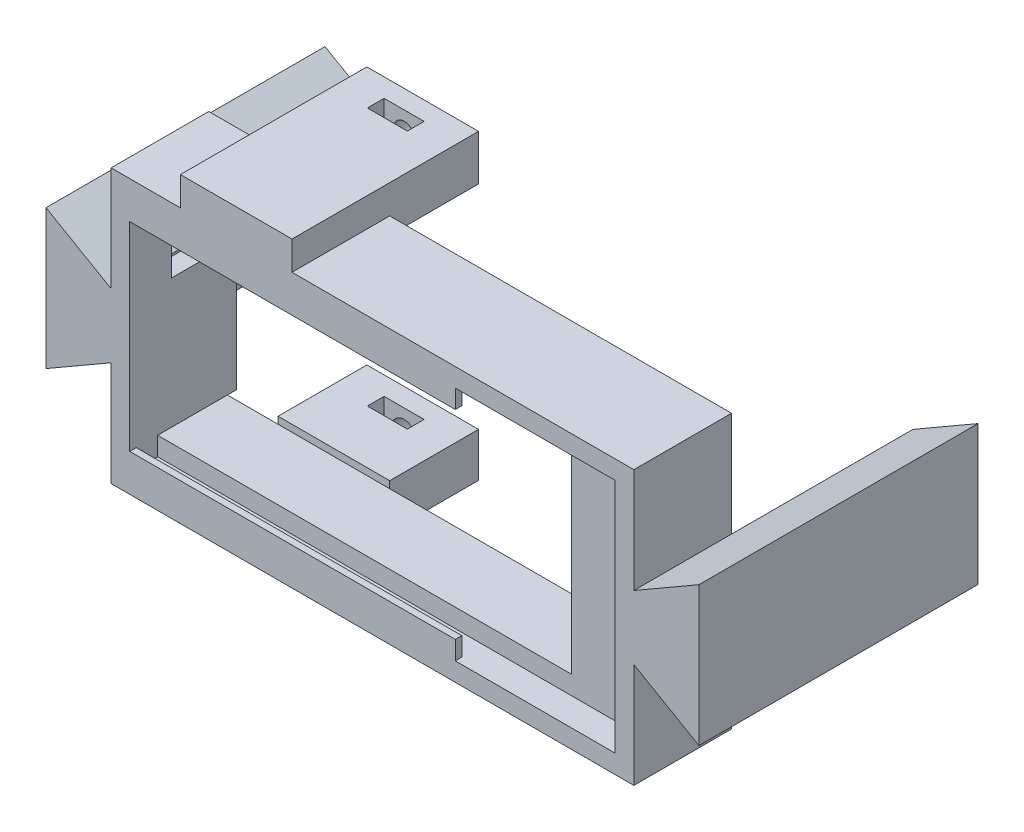
SolidWorks part; units mm, degrees
ref_plane "Front Plane" through (0, 0, 0) normal (0, 0, 1) x (1, 0, 0)
ref_plane "Top Plane" through (0, 0, 0) normal (0, 1, 0) x (1, 0, 0)
ref_plane "Right Plane" through (0, 0, 0) normal (1, 0, 0) x (0, 0, -1)
sketch "Sketch1" plane through (0, 0, 0) normal (0, 0, 1) x (1, 0, 0)
  line L0 (24.1, 10.7) -> (-24.1, 10.7)
  line L1 (26.1, -12.7) -> (-26.1, -12.7)
  line L2 (26.1, -12.7) -> (26.1, 12.7)
  line L3 (26.1, 12.7) -> (-26.1, 12.7)
  line L4 (-26.1, -12.7) -> (-26.1, 12.7)
  line L5 (26.1, -12.7) -> (-26.1, 12.7) construction
  line L6 (26.1, 12.7) -> (-26.1, -12.7) construction
  line L7 (-24.1, -10.7) -> (-24.1, 10.7)
  line L8 (24.1, -10.7) -> (-24.1, -10.7)
  line L9 (24.1, -10.7) -> (24.1, 10.7)
  line L10 (18.4, 10.7) -> (18.4, -10.7)
  point P0 (0, 0)
  dimension "D1" = 25.4
  dimension "D2" = 52.2
  dimension "D4" = 5.7
  dimension "D3" = 2
extrude "Boss-Extrude1" add sketch "Sketch1" along normal blind 7.5 contours L0 L10 L8 L9 | L4 L1 L2 L3 L9 L8 L7 L0 region at (21.25, 0, 0) region at (0, -12.1195, 0)
sketch "Sketch2" plane through (0, 0, 7.5) normal (0, 0, 1) x (1, 0, 0)
  line L12 (-26.1, -12.7) -> (-26.1, 12.7) construction
  line L13 (26.1, 12.7) -> (-26.1, 12.7) construction
  line L14 (26.1, -12.7) -> (-26.1, -12.7) construction
  line L15 (26.1, -12.7) -> (26.1, 12.7) construction
  line L16 (26.1, -12.7) -> (-26.1, -12.7)
  line L17 (-26.1, -12.7) -> (-26.1, 12.7)
  line L18 (26.1, 12.7) -> (-26.1, 12.7)
  line L19 (26.1, -12.7) -> (26.1, 12.7)
  line L20 (28.1, 14.7) -> (-28.1, 14.7)
  line L21 (-28.1, -14.7) -> (-28.1, 14.7)
  line L22 (28.1, -14.7) -> (-28.1, -14.7)
  line L23 (28.1, -14.7) -> (28.1, 14.7)
  line M29 (-26.1, 12.7) -> (-26.1, -12.7)
  line M30 (-26.1, -12.7) -> (26.1, -12.7)
  line M31 (26.1, -12.7) -> (26.1, 12.7)
  line M32 (26.1, 12.7) -> (-26.1, 12.7)
  dimension "D1" = 2
extrude "Boss-Extrude2" add sketch "Sketch2" along normal blind 3 and the other way up to surface (7.5 mm away) contours L22 L23 L20 L21 M29 M32 M31 M30 region at (27.4657, 0, 7.5) other way up to face at (-2.85, 0, 0)
sketch "Sketch3" plane through (0, 0, 0) normal (0, 0, 1) x (1, 0, 0)
  line L3 (-20.65, -11.4) -> (-8.65, -11.4)
  line L5 (-8.65, 11.4) -> (-20.65, 11.4)
  line L6 (-20.65, 11.4) -> (-20.65, -11.4)
  line L7 (-8.65, 11.4) -> (-8.65, -11.4)
  line L9 (-24.1, -10.7) -> (-24.1, 10.7) construction
  circle A0 centre (-14.65, 6.7) radius 2.5
  point P2 (-8.65, 0)
  point P10 (-14.65, 11.4)
  dimension "D1" = 5
  dimension "D3" = 4.7
  dimension "D2" = 12
  dimension "D4" = 22.8
  dimension "D5" = 9.45
sketch "Sketch4" plane through (0, 0, 0) normal (0, 0, -1) x (-1, 0, 0)
  line L2 (8.65, -11.4) -> (8.65, -16.25)
  line L3 (8.65, -16.25) -> (20.65, -16.25)
  line L18 (8.65, 16.25) -> (20.65, 16.25)
  line L20 (20.65, -16.25) -> (8.65, -16.25)
  line L22 (20.65, -11.4) -> (8.65, -11.4) construction
  line L23 (20.65, 11.4) -> (20.65, -11.4) construction
  line L24 (20.65, -16.25) -> (20.65, -11.4)
  line L25 (20.65, 11.4) -> (20.65, 16.25)
  line L26 (20.65, 16.25) -> (8.65, 16.25)
  line L27 (8.65, 16.25) -> (8.65, 11.4)
  line L28 (8.65, 11.4) -> (20.65, 11.4) construction
  line L29 (8.65, 11.4) -> (8.65, -11.4) construction
  line L30 (20.65, -11.4) -> (8.65, -11.4)
  line L31 (20.65, 11.4) -> (20.65, -11.4)
  line L32 (8.65, 11.4) -> (20.65, 11.4)
  line L33 (8.65, 11.4) -> (8.65, -11.4)
  point P3 (3.7, 16.25)
  point P5 (25.4, 16.25)
  point P6 (25.4, -16.25)
  point P7 (3.7, -16.25)
  dimension "D1" = 4.85
  dimension "D2" = 4.85
extrude "Boss-Extrude4" [suppressed] add sketch "Sketch4" along normal blind 3 and the other way up to surface separate body
sketch "Sketch6" plane through (0, 0, 10.5) normal (0, 0, 1) x (1, 0, 0)
  line L1 (-28.1, 3.45) -> (-35.1, 7.4915)
  line L5 (-28.1, -14.7) -> (-28.1, 14.7) construction
  line L7 (-35.1, 7.4915) -> (-35.1, -7.4915)
  line L8 (0, 10.5) -> (0, 0) construction
  line L16 (-35.1, -7.4915) -> (-28.1, -3.45)
  line L17 (-28.1, 3.45) -> (-28.1, -3.45)
  point P6 (-35.1, 0)
  dimension "D1" = 7
  dimension "D2" = 6.9
  dimension "D3" = 60
  dimension "D4" = 60
extrude "Boss-Extrude5" add sketch "Sketch6" against normal blind 30
mirror "Mirror1" about plane through (0, 0, 0) normal (1, 0, 0) of "Boss-Extrude5"
ref_plane "Plane1" through (-8.65, 0, 0) normal (1, 0, 0) x (0, 0, -1)
ref_plane "Plane2" through (-20.65, 0, 0) normal (1, 0, 0) x (0, 0, -1)
sketch "Sketch10" plane through (-8.65, 0, 0) normal (1, 0, 0) x (0, 0, -1)
  line L1 (9.55, 17.8) -> (-10.5, 17.8)
  line L3 (0, 14.7) -> (-10.5, 14.7)
  line L6 (-10.5, 14.7) -> (-10.5, 17.8)
  line L7 (19.5, 7.4915) -> (-10.5, 7.4915) construction
  line L8 (0, 12.9) -> (0, 14.7)
  line L9 (0, 12.9) -> (9.55, 12.9)
  line L10 (9.55, 12.9) -> (9.55, 17.8)
  dimension "D3" = 3.1
  dimension "D4" = 5.4085
extrude "Boss-Extrude12" add sketch "Sketch10" against normal up to surface (12 mm away) contours L9 L10 L1 L8 region at (-8.65, 15.7192, -0.6624) up to plane "Plane2"
sketch "Sketch11" plane through (0, 0, -9.55) normal (0, 0, -1) x (-1, 0, 0)
  line L0 (14.1, 17.8) -> (14.1, 16.6)
  line L1 (20.65, 17.8) -> (8.65, 17.8) construction
  line L3 (15.2, 16.6) -> (15.2, 17.8)
  line L4 (20.65, 17.8) -> (8.65, 17.8)
  arc A0 (15.2, 16.6) -> (14.1, 16.6) centre (14.65, 15.6474) cw
  arc A1 (14.1, 16.6) -> (15.2, 16.6) centre (14.65, 15.6474) cw
  point P8 (14.65, 17.8)
  dimension "D3" = 1.1
  dimension "D1" = 1.1
  dimension "D2" = 1.2
extrude "Cut-Extrude2" cut sketch "Sketch11" against normal blind 16 contours A1 A0 region at (-14.65, 15.6474, -9.55)
sketch "Sketch12" plane through (0, 17.8, 0) normal (0, 1, 0) x (1, 0, 0)
  line L0 (-13.55, 9.55) -> (-15.75, 9.55) construction
  line L1 (-13.55, 9.55) -> (-15.75, 9.55)
  line L3 (-12.5, 5.75) -> (-16.8, 5.75)
  line L4 (-16.8, 5.75) -> (-16.8, 7.55)
  line L5 (-16.8, 7.55) -> (-12.5, 7.55)
  line L6 (-12.5, 7.55) -> (-12.5, 5.75)
  point P7 (-14.65, 7.55)
  point P8 (-14.65, 9.55)
  dimension "D1" = 2
  dimension "D2" = 1.8
  dimension "D3" = 4.3
extrude "Cut-Extrude3" cut sketch "Sketch12" against normal up to next contours L6 L5 L4 L3 region at (-14.65, 17.8, -6.65)
sketch "Sketch13" plane through (-8.65, 0, 0) normal (1, 0, 0) x (0, 0, -1)
  line L4 (0, -14.7) -> (0, -9.95)
  line L8 (0, -9.95) -> (9.55, -9.95)
  line L9 (9.55, -9.95) -> (9.55, -14.7)
  line L10 (9.55, -14.7) -> (0, -14.7)
  line L11 (0, -14.7) -> (-10.5, -14.7) construction
  line L12 (0, 11.4) -> (0, -11.4) construction
  dimension "D1" = 4.75
  dimension "D3" = 9.55
extrude "Boss-Extrude14" add sketch "Sketch13" against normal up to surface (12 mm away) separate body contours L10 L9 L8 L4 region at (-8.65, -12.325, -4.775) up to plane "Plane2"
sketch "Sketch8" plane through (0, 0, 0) normal (0, 0, -1) x (-1, 0, 0)
  line L1 (-18.4, 10.7) -> (-26.1, 10.7)
  line L2 (-18.4, 10.7) -> (-18.4, -10.7)
  line L3 (-18.4, -10.7) -> (-26.1, -10.7)
  line L4 (-26.1, 10.7) -> (-26.1, -10.7)
  line L5 (-18.4, -10.7) -> (24.1, -10.7) construction
  line L6 (-28.1, 14.7) -> (-28.1, 3.45) construction
  dimension "D1" = 2
extrude "Boss-Extrude6" [suppressed] add sketch "Sketch8" along normal blind 3.5
sketch "Sketch9" [suppressed] plane through (0, 0, -3.5) normal (0, 0, -1) x (-1, 0, 0)
  line L0 (-18.4, 10.7) -> (-26.1, 10.7) construction
  line L1 (-18.4, 10.7) -> (-26.1, 10.7)
  circle A0 centre (-22.25, 0) radius 2.65
  point P7 (-22.25, 10.7)
  dimension "D1" = 5.3
extrude "Cut-Extrude1" [suppressed] cut sketch "Sketch9" against normal through all contours A0
sketch "Sketch14" plane through (0, 0, -9.55) normal (0, 0, -1) x (-1, 0, 0)
  line L0 (14.1, -14.7) -> (14.1, -13.5)
  line L1 (20.65, -14.7) -> (8.65, -14.7) construction
  line L2 (15.2, -14.7) -> (15.2, -13.5)
  line L3 (15.2, -14.7) -> (14.1, -14.7)
  line L4 (20.65, -14.7) -> (8.65, -14.7)
  circle A1 centre (14.65, -12.3221) radius 1.3
  point P8 (14.65, -14.7)
  point P9 (14.65, -14.7)
  dimension "D3" = 2.6
  dimension "D1" = 1.1
  dimension "D2" = 1.2
extrude "Cut-Extrude4" cut sketch "Sketch14" against normal blind 16 contours A1 region at (-14.65, -12.3221, -9.55)
sketch "Sketch15" plane through (0, -14.7, 0) normal (0, -1, 0) x (1, 0, 0)
  line L0 (-16.8, -7.55) -> (-12.5, -7.55) construction
  line L1 (-12.5, -7.55) -> (-12.5, -5.75) construction
  line L2 (-12.5, -5.75) -> (-16.8, -5.75) construction
  line L3 (-16.8, -5.75) -> (-16.8, -7.55) construction
  line L4 (-16.8, -7.55) -> (-12.5, -7.55)
  line L5 (-12.5, -7.55) -> (-12.5, -5.75)
  line L6 (-12.5, -5.75) -> (-16.8, -5.75)
  line L7 (-16.8, -5.75) -> (-16.8, -7.55)
extrude "Cut-Extrude5" cut sketch "Sketch15" against normal blind 10
sketch "Sketch16" plane through (0, 0, 0) normal (0, 0, -1) x (-1, 0, 0)
  line L0 (24.1, 10.7) -> (28.1, 10.7)
  line L2 (24.1, -10.7) -> (24.1, 10.7)
  line L3 (24.1, -10.7) -> (28.1, -10.7)
  line L4 (28.1, -10.7) -> (28.1, 10.7)
  line L7 (28.1, 14.7) -> (28.1, 3.45) construction
extrude "Cut-Extrude6" cut sketch "Sketch16" against normal blind 4
sketch "Sketch17" plane through (0, 0, 10.5) normal (0, 0, 1) x (1, 0, 0)
  line L0 (8.9, 12.7) -> (-26.1, 12.7)
  line L1 (26.1, 12.7) -> (-26.1, 12.7) construction
  line L2 (-26.1, 12.7) -> (-26.1, -12.7)
  line L3 (-26.1, -12.7) -> (8.9, -12.7)
  line L4 (-26.1, -12.7) -> (26.1, -12.7) construction
  line L5 (8.9, -12.7) -> (8.9, -10.7)
  line L6 (18.4, 10.7) -> (-24.1, 10.7) construction
  line L7 (18.4, 10.7) -> (-24.1, 10.7)
  line L8 (18.4, -10.7) -> (-24.1, -10.7) construction
  line L9 (18.4, -10.7) -> (-24.1, -10.7)
  line L10 (8.9, 10.7) -> (8.9, 12.7)
  line L11 (-24.1, 10.7) -> (-26.1, 10.7)
  line L12 (-24.1, -10.7) -> (-26.1, -10.7)
  line M6 (-26.1, -12.7) -> (-26.1, 12.7)
  line M7 (-26.1, 12.7) -> (26.1, 12.7)
  line M9 (26.1, -12.7) -> (-26.1, -12.7)
  dimension "D1" = 35
extrude "Boss-Extrude15" add sketch "Sketch17" against normal blind 0.7 contours L7 L10 L2 M7 | L5 L9 M6 M9 region at (-8.6, 11.7, 10.5) region at (-8.6, -11.7, 10.5)
sketch "Sketch18" plane through (0, 0, 0) normal (0, 0, -1) x (-1, 0, 0)
  circle A0 centre (14.65, -12.3221) radius 1.3 construction
  circle A1 centre (14.65, -12.3221) radius 1.3
extrude "Cut-Extrude7" cut sketch "Sketch18" against normal blind 6
sketch "Sketch19" plane through (0, 0, 7.5) normal (0, 0, 1) x (1, 0, 0)
  line L0 (8.9, -10.7) -> (-26.1, -10.7) construction
  line L1 (-24.1, -10.7) -> (-24.1, 10.7) construction
  line L2 (8.9, 10.7) -> (-26.1, 10.7) construction
  line L3 (-26.1, 10.7) -> (-26.1, -10.7) construction
  line L4 (8.9, -10.7) -> (-26.1, -10.7)
  line L5 (-24.1, -10.7) -> (-24.1, 10.7)
  line L6 (8.9, 10.7) -> (-26.1, 10.7)
  line L7 (-26.1, 10.7) -> (-26.1, -10.7)
  line M4 (-24.1, -10.7) -> (-24.1, 10.7)
  line M5 (-26.1, 12.7) -> (-26.1, -12.7)
extrude "Cut-Extrude8" cut sketch "Sketch19" against normal blind 14 contours L6 L4 M4 M5 region at (-25.1, 0, 7.5)
sketch "Sketch20" plane through (0, 0, 4) normal (0, 0, -1) x (-1, 0, 0)
  line L0 (26.1, 10.7) -> (28.1, 10.7)
  line L1 (28.1, 10.7) -> (28.1, 3.2)
  line L2 (28.1, 3.45) -> (28.1, 10.7) construction
  line L3 (28.1, 3.2) -> (26.1, 3.2)
  line L4 (26.1, 10.7) -> (26.1, -10.7) construction
  line L5 (26.1, 3.2) -> (26.1, 10.7)
  dimension "D1" = 7.5
extrude "Cut-Extrude9" cut sketch "Sketch20" against normal blind 2
sketch "Sketch21" plane through (0, 0, 4) normal (0, 0, -1) x (-1, 0, 0)
  line L0 (26.1, -10.7) -> (28.1, -10.7) construction
  line L1 (28.1, -10.7) -> (28.1, -3.45) construction
  line L2 (26.1, 3.2) -> (26.1, -10.7) construction
  line L3 (26.1, 3.2) -> (28.1, 3.2) construction
  line L4 (26.1, -10.7) -> (28.1, -10.7)
  line L5 (28.1, -10.7) -> (28.1, -3.45)
  line L6 (26.1, 3.2) -> (26.1, -10.7)
  line L7 (26.1, 3.2) -> (28.1, 3.2)
  line M1 (28.1, -3.45) -> (28.1, 3.2)
  line M2 (28.1, 3.2) -> (26.1, 3.2)
  line M3 (26.1, 3.2) -> (26.1, -10.7)
  line M4 (26.1, -10.7) -> (28.1, -10.7)
  line M5 (28.1, -10.7) -> (28.1, -3.45)
extrude "Boss-Extrude16" add sketch "Sketch21" along normal blind 5 contours M5 M1 M2 M3 M4 region at (-27.1, -3.75, 4)
